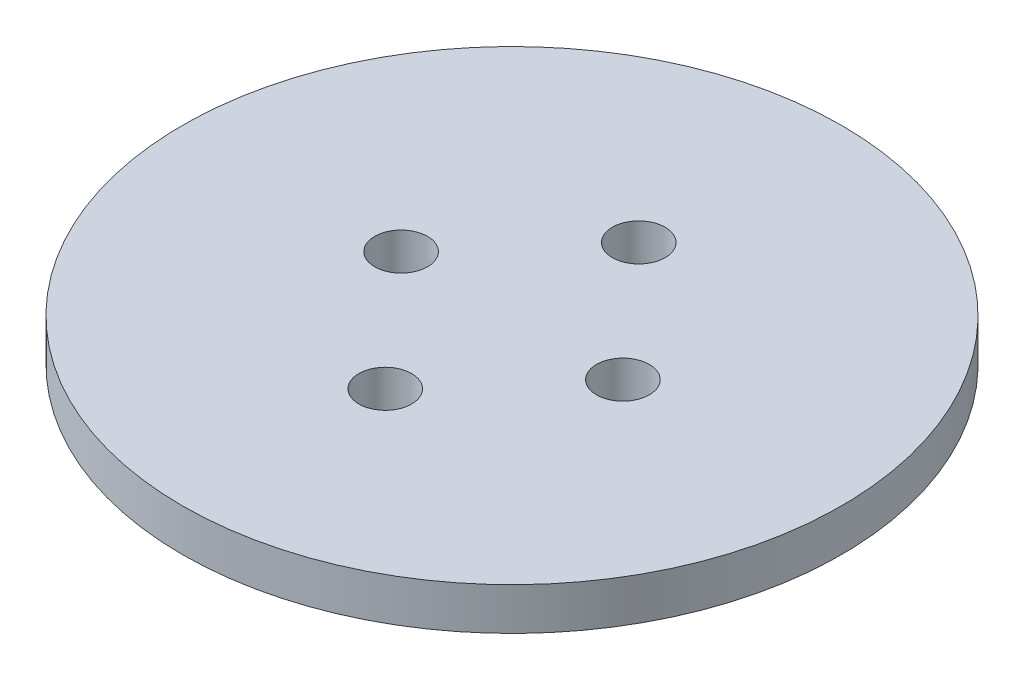
SolidWorks part; units mm, degrees
material "Pine"
ref_plane "Front Plane" through (0, 0, 0) normal (0, 0, 1) x (1, 0, 0)
ref_plane "Top Plane" through (0, 0, 0) normal (0, 1, 0) x (1, 0, 0)
ref_plane "Right Plane" through (0, 0, 0) normal (1, 0, 0) x (0, 0, -1)
sketch "Sketch1" plane through (0, 0, 0) normal (0, 1, 0) x (1, 0, 0)
  circle A0 centre (0, 0) radius 49.53
  dimension "D1" = 99.06
extrude "Boss-Extrude1" add sketch "Sketch1" along normal blind 6.35
hole_wizard "Threaded Rod Holes" positions "Sketch2" profile "Sketch3" tap size "5/16-18" standard "ANSI Inch" end condition through all
sketch "Sketch2" plane through (0, 6.35, 0) normal (0, 1, 0) x (1, 0, 0)
  line L0 (0, 19.05) -> (0, 0) construction
  line L1 (0, 0) -> (0, -19.05) construction
  point P16 (0, 19.05)
  point P23 (0, -19.05)
  dimension "D1" = 38.1
sketch "Sketch3" plane through (0, 6.35, -19.05) normal (1, 0, 0) x (0, 0, 1)
  line L0 (0, 0) -> (0, 6.35)
  line L1 (0, 6.35) -> (3.9687, 6.35)
  line L2 (3.9687, 6.35) -> (3.9687, 0)
  line L5 (3.9687, 0) -> (0, 0)
  line L11 (0, -6.35) -> (0, 107.95) construction
  dimension "Thru Tap Drill Dia." = 7.9375
  dimension "Thru Tap Drill Depth" = 6.35
cosmetic thread "Hole Thread1" parameters "D2"=7.9375
cosmetic thread "Hole Thread2" parameters "D2"=7.9375
hole_wizard "U-Bolt Holes" positions "Sketch4" profile "Sketch5" tap size "5/16-18" standard "ANSI Inch" end condition through all
sketch "Sketch4" plane through (0, 6.35, 0) normal (0, 1, 0) x (1, 0, 0)
  line L0 (0, 0) -> (0, 14.8177) construction
  point P0 (-16.6687, 0)
  point P10 (16.6687, 0)
  dimension "D1" = 33.3375
sketch "Sketch5" plane through (-16.6687, 6.35, 0) normal (1, 0, 0) x (0, 0, 1)
  line L0 (0, 0) -> (0, 6.35)
  line L1 (0, 6.35) -> (3.9687, 6.35)
  line L2 (3.9687, 6.35) -> (3.9687, 0)
  line L5 (3.9687, 0) -> (0, 0)
  line L11 (0, -6.35) -> (0, 107.95) construction
  dimension "Thru Tap Drill Dia." = 7.9375
  dimension "Thru Tap Drill Depth" = 6.35
cosmetic thread "Hole Thread3" parameters "D2"=7.9375
cosmetic thread "Hole Thread4" parameters "D2"=7.9375
